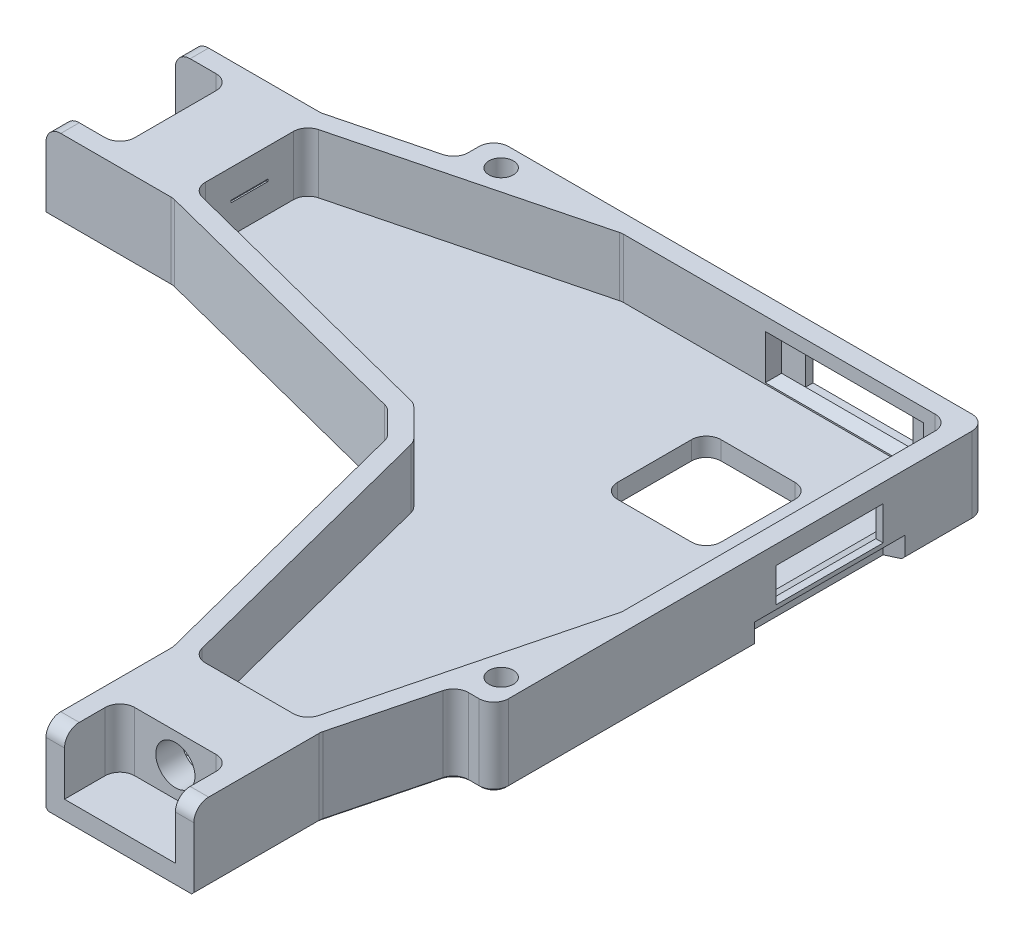
SolidWorks part; units mm, degrees
ref_plane "Front Plane" through (0, 0, 0) normal (0, 0, 1) x (1, 0, 0)
ref_plane "Top Plane" through (0, 0, 0) normal (0, 1, 0) x (1, 0, 0)
ref_plane "Right Plane" through (0, 0, 0) normal (1, 0, 0) x (0, 0, -1)
sketch "x Sensor" plane through (0, 0, 0) normal (0, 0, 1) x (1, 0, 0)
  line L0 (-13, 0) -> (0, 0) construction
  line L1 (-22.5, 1.5) -> (-13, 1.5)
  line L2 (-22.5, 1.5) -> (-22.5, -1.5)
  line L3 (-22.5, -1.5) -> (-13, -1.5)
  line L4 (-13, 1.5) -> (-13, -1.5)
  point P4 (-13, 0)
  dimension "D1" = 13
  dimension "D2" = 3
  dimension "D3" = 9.5
sketch "y Sensor" plane through (0, 0, 0) normal (1, 0, 0) x (0, 0, -1)
  line L0 (-13, 0) -> (0, 0) construction
  line L1 (-13, 1.5) -> (-22.5, 1.5)
  line L2 (-13, 1.5) -> (-13, -1.5)
  line L3 (-13, -1.5) -> (-22.5, -1.5)
  line L4 (-22.5, 1.5) -> (-22.5, -1.5)
  line L5 (0, 1.5) -> (0, -1.5) construction
  dimension "D1" = 9.5
  dimension "D2" = 13
ref_plane "y LED plane" through (-80, 0, 0) normal (1, 0, 0) x (0, 0, -1)
ref_plane "x LED plane" through (0, 0, 80) normal (0, 0, 1) x (1, 0, 0)
sketch "y LED" plane through (-80, 0, 0) normal (1, 0, 0) x (0, 0, -1)
  line L0 (-17.75, 1.5) -> (-17.75, -1.5) construction
  line L1 (-13, 1.5) -> (-22.5, 1.5) construction
  line L2 (-13, -1.5) -> (-22.5, -1.5) construction
  line L3 (-25.25, 0) -> (-10.25, 0) construction
  line L4 (-13, 0) -> (0, 0) construction
  point P10 (-17.75, 0)
  point P11 (-17.75, 0)
  dimension "D1" = 15
sketch "x LED" plane through (0, 0, 80) normal (0, 0, 1) x (1, 0, 0)
  line L0 (-17.75, 1.5) -> (-17.75, -1.5) construction
  line L1 (-22.5, 1.5) -> (-13, 1.5) construction
  line L2 (-22.5, -1.5) -> (-13, -1.5) construction
  line L3 (-25.25, 0) -> (-10.25, 0) construction
  point P9 (-17.75, 0)
  point P10 (-17.75, 0)
  dimension "D1" = 15
ref_plane "y LED cross-plane" through (0, 0, 17.75) normal (0, 0, 1) x (0, -1, 0)
ref_plane "x LED cross-plane" through (-17.75, 0, 0) normal (1, 0, 0) x (0, -1, 0)
ref_plane "Floor plane" through (0, -4, 0) normal (0, 1, 0) x (1, 0, 0)
ref_plane "Ceiling plane" through (0, 4, 0) normal (0, 1, 0) x (1, 0, 0)
sketch "Sketch10" plane through (0, -4, 0) normal (0, 1, 0) x (1, 0, 0)
  line L0 (0, 0) -> (-40, 0)
  line L1 (-40, 0) -> (-80, -10.25)
  line L2 (-80, -25.25) -> (-80, -10.25) construction
  line L3 (-80, -10.25) -> (-95, -10.25)
  line L4 (-95, -10.25) -> (-95, -25.25) construction
  line L5 (-95, -25.25) -> (-80, -25.25)
  line L6 (-80, -25.25) -> (-40, -35.5)
  line L7 (-40, -35.5) -> (-35.5, -40)
  line L8 (-35.5, -40) -> (-25.25, -80)
  line L9 (-25.25, -80) -> (-10.25, -80) construction
  line L10 (-25.25, -80) -> (-25.25, -95)
  line L11 (-25.25, -95) -> (-10.25, -95) construction
  line L12 (-10.25, -95) -> (-10.25, -80)
  line L13 (-10.25, -80) -> (0, -40)
  line L14 (0, -40) -> (0, 0)
  line L15 (-95, -17.75) -> (-65.0259, -17.75) construction
  line L16 (-17.75, -95) -> (-17.75, -69.9842) construction
  line L17 (-40.3152, 2.5) -> (-80.3152, -7.75)
  line L18 (-80.3152, -7.75) -> (-97.5, -7.75)
  line L19 (-97.5, -7.75) -> (-97.5, -10.25)
  line L20 (-97.5, -27.75) -> (-80.3152, -27.75)
  line L21 (-80.3152, -27.75) -> (-41.2837, -37.7518)
  line L22 (-41.2837, -37.7518) -> (-37.7518, -41.2837)
  line L23 (-37.7518, -41.2837) -> (-27.75, -80.3152)
  line L24 (-27.75, -80.3152) -> (-27.75, -97.5)
  line L25 (-27.75, -97.5) -> (-25.25, -97.5)
  line L26 (-7.75, -97.5) -> (-7.75, -80.3152)
  line L27 (-7.75, -80.3152) -> (2.5, -40.3152)
  line L28 (2.5, -40.3152) -> (2.5, 2.5)
  line L29 (2.5, 2.5) -> (-40.3152, 2.5)
  line L30 (-95, -10.25) -> (-97.5, -10.25)
  line L31 (-95, -25.25) -> (-97.5, -25.25)
  line L32 (-97.5, -10.25) -> (-97.5, -25.25) construction
  line L33 (-97.5, -7.75) -> (-97.5, -27.75) construction
  line L34 (-97.5, -25.25) -> (-97.5, -27.75)
  line L35 (-25.25, -95) -> (-25.25, -97.5)
  line L36 (-10.25, -95) -> (-10.25, -97.5)
  line L37 (-25.25, -97.5) -> (-10.25, -97.5) construction
  line L38 (-27.75, -97.5) -> (-7.75, -97.5) construction
  line L39 (-10.25, -97.5) -> (-7.75, -97.5)
  dimension "D1" = 45
  dimension "D2" = 40
  dimension "D3" = 15
  dimension "D4" = 2.5
sketch "Max Shadows" plane through (0, 0, 0) normal (0, 1, 0) x (1, 0, 0)
  line L0 (-80, -17.75) -> (0, -13) construction
  line L1 (0, -13) -> (0, -22.5) construction
  line L2 (0, -22.5) -> (-80, -17.75) construction
  line L3 (0, -40) -> (0, 0) construction
  line L4 (-17.75, -80) -> (-22.5, 0) construction
  line L5 (-25.25, -80) -> (-10.25, -80) construction
  line L6 (-22.5, 0) -> (-13, 0) construction
  line L7 (0, 0) -> (-40, 0) construction
  line L8 (-17.75, -80) -> (-13, 0) construction
extrude "Boss-Extrude3" add sketch "Sketch10" along normal up to surface (8 mm away) up to plane "Ceiling plane"
sketch "Sketch12" plane through (0, -4, 0) normal (0, 1, 0) x (1, 0, 0)
  line L0 (-97.5, -10.25) -> (-97.5, -25.25) construction
  line L1 (-97.5, -7.75) -> (-97.5, -10.25) construction
  line L2 (-80.3152, -7.75) -> (-97.5, -7.75) construction
  line L3 (-40.3152, 2.5) -> (-80.3152, -7.75) construction
  line L4 (2.5, 2.5) -> (-40.3152, 2.5) construction
  line L5 (2.5, -40.3152) -> (2.5, 2.5) construction
  line L6 (-7.75, -80.3152) -> (2.5, -40.3152) construction
  line L7 (-7.75, -97.5) -> (-7.75, -80.3152) construction
  line L8 (-10.25, -97.5) -> (-7.75, -97.5) construction
  line L9 (-25.25, -97.5) -> (-10.25, -97.5) construction
  line L10 (-27.75, -97.5) -> (-25.25, -97.5) construction
  line L11 (-27.75, -80.3152) -> (-27.75, -97.5) construction
  line L12 (-37.7518, -41.2837) -> (-27.75, -80.3152) construction
  line L13 (-97.5, -25.25) -> (-97.5, -27.75) construction
  line L14 (-97.5, -27.75) -> (-80.3152, -27.75) construction
  line L15 (-80.3152, -27.75) -> (-41.2837, -37.7518) construction
  line L16 (-41.2837, -37.7518) -> (-37.7518, -41.2837) construction
  line L17 (-97.5, -10.25) -> (-97.5, -25.25)
  line L18 (-97.5, -7.75) -> (-97.5, -10.25)
  line L19 (-80.3152, -7.75) -> (-97.5, -7.75)
  line L20 (-40.3152, 2.5) -> (-80.3152, -7.75)
  line L21 (2.5, 2.5) -> (-40.3152, 2.5)
  line L22 (2.5, -40.3152) -> (2.5, 2.5)
  line L23 (-7.75, -80.3152) -> (2.5, -40.3152)
  line L24 (-7.75, -97.5) -> (-7.75, -80.3152)
  line L25 (-10.25, -97.5) -> (-7.75, -97.5)
  line L26 (-25.25, -97.5) -> (-10.25, -97.5)
  line L27 (-27.75, -97.5) -> (-25.25, -97.5)
  line L28 (-27.75, -80.3152) -> (-27.75, -97.5)
  line L29 (-37.7518, -41.2837) -> (-27.75, -80.3152)
  line L30 (-97.5, -25.25) -> (-97.5, -27.75)
  line L31 (-97.5, -27.75) -> (-80.3152, -27.75)
  line L32 (-80.3152, -27.75) -> (-41.2837, -37.7518)
  line L33 (-41.2837, -37.7518) -> (-37.7518, -41.2837)
extrude "Boss-Extrude4" add sketch "Sketch12" against normal blind 2.5
sketch "Sketch13" plane through (0, 0, 17.75) normal (0, 0, 1) x (0, -1, 0)
  line L0 (-4, -80) -> (-0.15, -80)
  line L1 (4, -80) -> (4, -84.05)
  line L2 (4, -97.5) -> (4, -80) construction
  line L3 (-4, -80) -> (4, -80) construction
  line L5 (0.15, -80) -> (4, -80)
  line L6 (-0.15, -80) -> (0.15, -80) construction
  line L8 (-0.15, -80) -> (-0.15, -80.2)
  line L9 (-4, -80) -> (-4, -90)
  line L10 (-4, -97.5) -> (-4, -80) construction
  line L11 (-4, -90) -> (4, -90)
  line L12 (4, -90) -> (4, -86.5)
  line L13 (4, -86.5) -> (-3, -86.5)
  line L14 (-3, -86.5) -> (-3, -83.05)
  line L15 (-0.15, -80.2) -> (-3, -83.05)
  line L16 (0, -80) -> (0, -86.5) construction
  line L17 (-2.5, -90) -> (-2.5, -86.5) construction
  line L18 (-2.5, -86.5) -> (-2.5, -85.2) construction
  line L19 (2.5, -90) -> (2.5, -86.5) construction
  line L20 (2.5, -86.5) -> (2.5, -85.2) construction
  line L21 (0.15, -80) -> (0.15, -80.2)
  line L22 (0.15, -80.2) -> (4, -84.05)
  arc A0 (-2.5, -85.2) -> (2.5, -85.2) centre (0, -85.2) cw construction
  point P13 (0, -80)
  point P26 (0, -82.7)
  dimension "D3" = 7.3
  dimension "D1" = 0.3
  dimension "D2" = 1
  dimension "D4" = 5
  dimension "D5" = 45
  dimension "D6" = 6.5
  dimension "D7" = 10
  dimension "D8" = 0.2
extrude "Boss-Extrude5" add sketch "Sketch13" along normal up to next and the other way up to next
sketch "Sketch14" plane through (-90, 0, 0) normal (-1, 0, 0) x (0, 0, 1)
  line L0 (17.75, 1.5) -> (17.75, -1.5) construction
  circle A0 centre (17.75, 0) radius 2.65
  dimension "D1" = 5.3
extrude "Cut-Extrude1" cut sketch "Sketch14" against normal up to next
sketch "Sketch15" plane through (-17.75, 0, 0) normal (1, 0, 0) x (0, -1, 0)
  line L0 (-4, -80) -> (-0.15, -80)
  line L1 (4, -80) -> (4, -84.05)
  line L2 (4, -80) -> (4, -97.5) construction
  line L3 (-4, -80) -> (4, -80) construction
  line L5 (0.15, -80) -> (4, -80)
  line L6 (-0.15, -80) -> (0.15, -80) construction
  line L8 (-0.15, -80) -> (-0.15, -80.2)
  line L9 (-4, -80) -> (-4, -90)
  line L11 (-4, -90) -> (4, -90)
  line L12 (4, -90) -> (4, -86.5)
  line L13 (4, -86.5) -> (-3, -86.5)
  line L14 (-3, -86.5) -> (-3, -83.05)
  line L15 (-0.15, -80.2) -> (-3, -83.05)
  line L16 (0, -80) -> (0, -86.5) construction
  line L17 (-2.5, -90) -> (-2.5, -86.5) construction
  line L18 (-2.5, -86.5) -> (-2.5, -85.2) construction
  line L19 (2.5, -90) -> (2.5, -86.5) construction
  line L20 (2.5, -86.5) -> (2.5, -85.2) construction
  line L21 (0.15, -80) -> (0.15, -80.2)
  line L22 (0.15, -80.2) -> (4, -84.05)
  arc A0 (-2.5, -85.2) -> (2.5, -85.2) centre (0, -85.2) cw construction
extrude "Boss-Extrude6" add sketch "Sketch15" along normal up to next and the other way up to next
sketch "Sketch16" plane through (0, 0, 90) normal (0, 0, -1) x (-1, 0, 0)
  circle A0 centre (17.75, 0) radius 2.65
extrude "Cut-Extrude2" cut sketch "Sketch16" along normal up to next
sketch "Sketch18" plane through (0, 0, -2.5) normal (0, 0, -1) x (-1, 0, 0)
  line L0 (-2.5, -6.5) -> (40.3152, -6.5) construction
  line L1 (-2.5, 4) -> (80.3152, 4)
  line L2 (-2.5, 4) -> (-2.5, -6.5)
  line L3 (-2.5, -6.5) -> (80.3152, -6.5)
  line L4 (80.3152, 4) -> (80.3152, -6.5)
  line L6 (80.3152, 4) -> (80.3152, -6.5) construction
extrude "Cut-Extrude4" cut sketch "Sketch18" against normal offset from surface (1.5 mm away) 1 up to face at (-20, 0, 0)
sketch "Sketch20" plane through (2.5, 0, 0) normal (1, 0, 0) x (0, 0, -1)
  line L0 (-40.3152, 4) -> (1, 4) construction
  line L1 (1, -6.5) -> (-80.3152, -6.5)
  line L2 (1, -6.5) -> (1, 4)
  line L3 (1, 4) -> (-80.3152, 4)
  line L4 (-80.3152, -6.5) -> (-80.3152, 4)
  line L5 (-80.3152, 4) -> (-80.3152, -6.5) construction
extrude "Cut-Extrude6" cut sketch "Sketch20" against normal offset from surface (1.5 mm away) 1 contours L1 L4 L3 L2 up to face at (0, 0, 20)
sketch "Sketch21" plane through (0, 0, 0) normal (0, 0, 1) x (1, 0, 0)
  line L0 (-40, -4) -> (-50.0713, -4)
  line L1 (-50.0713, -4) -> (-50.0713, 4)
  line L2 (-50.0713, 4) -> (-40, 4)
  line L3 (-46.1689, 4) -> (-80.3152, 4) construction
  line L4 (0, 4) -> (-40, 4)
  line L5 (-40, 4) -> (-40, -4)
  line L6 (-40, -4) -> (0, -4)
  line L7 (0, -4) -> (0, 4)
  line L8 (0, 4) -> (-40, 4)
  line L10 (-40, -4) -> (0, -4)
  line L11 (0, -4) -> (0, 4)
  dimension "D1" = 0
extrude "Boss-Extrude7" add sketch "Sketch21" along normal offset from surface (1.5 mm away) 2.5 up to face at (-22.5844, -1.25, -1)
sketch "Sketch22" plane through (0, 0, 0) normal (-1, 0, 0) x (0, 0, 1)
  line L0 (40, -4) -> (50.0713, -4)
  line L1 (50.0713, -4) -> (50.0713, 4)
  line L2 (50.0713, 4) -> (40, 4)
  line L4 (1.5, 4) -> (1.5, -4)
  line L5 (1.5, -4) -> (40, -4)
  line L6 (40, -4) -> (40, 4)
  line L7 (40, 4) -> (1.5, 4)
  line L8 (1.5, 4) -> (1.5, -4)
  line L9 (1.5, -4) -> (40, -4)
  line L11 (40, 4) -> (1.5, 4)
  dimension "D1" = 0
extrude "Boss-Extrude8" add sketch "Sketch22" along normal offset from surface (1.5 mm away) 2.5 up to face at (1, -1.25, 22.5844)
sketch "Sketch17" plane through (0, 0, 0) normal (0, 0, 1) x (1, 0, 0)
  line L1 (-8, -3.1) -> (-22.5, -3.1)
  line L2 (-8, -3.1) -> (-8, 1.5)
  line L3 (-8, 1.5) -> (-22.5, 1.5)
  line L4 (-22.5, -3.1) -> (-22.5, 1.5)
  dimension "D1" = 14.5
  dimension "D2" = 4.6
extrude "Cut-Extrude3" cut sketch "Sketch17" against normal through all and the other way up to next
sketch "Sketch19" plane through (0, 0, 0) normal (1, 0, 0) x (0, 0, -1)
  line L1 (-13, -3.1) -> (-27.5, -3.1)
  line L2 (-13, -3.1) -> (-13, 1.5)
  line L3 (-13, 1.5) -> (-27.5, 1.5)
  line L4 (-27.5, -3.1) -> (-27.5, 1.5)
  dimension "D1" = 14.5
  dimension "D2" = 4.6
extrude "Cut-Extrude5" cut sketch "Sketch19" along normal through all and the other way up to next
sketch "Sketch23" plane through (-1.5, 0, 0) normal (-1, 0, 0) x (0, 0, 1)
  line L0 (27.5, -3.1) -> (13, -3.1) construction
  line L1 (10.25, 1.5) -> (30.25, 1.5)
  line L2 (10.25, 1.5) -> (10.25, -3.1)
  line L3 (10.25, -3.1) -> (30.25, -3.1)
  line L4 (30.25, 1.5) -> (30.25, -3.1)
  point P4 (20.25, -3.1)
  point P7 (20.25, -3.1)
  dimension "D1" = 20
extrude "Cut-Extrude7" cut sketch "Sketch23" against normal up to surface (1.5 mm away) up to plane "Right Plane"
sketch "Sketch25" plane through (-36, 0, 1.5) normal (0, 0, 1) x (1, 0, 0)
  line L0 (13.5, 1.5) -> (28, 1.5) construction
  line L1 (10.25, 1.5) -> (30.25, 1.5)
  line L2 (10.25, 1.5) -> (10.25, -3.1)
  line L3 (10.25, -3.1) -> (30.25, -3.1)
  line L4 (30.25, 1.5) -> (30.25, -3.1)
extrude "Cut-Extrude9" cut sketch "Sketch25" against normal up to surface (1.5 mm away) up to plane "Front Plane"
chamfer "Chamfer2" distance 1.5 angle 25 8 edges at (-1.5, -3.1, 20.25) (-1.5, -0.8, 30.25) (-1.5, 1.5, 20.25) (-1.5, -0.8, 10.25) (-5.75, -0.8, 1.5) (-15.75, 1.5, 1.5) (-25.75, -0.8, 1.5) (-15.75, -3.1, 1.5) first distance on face at (-0.125, -3.1, 20.25) first distance on face at (-0.75, -0.8, 30.25) first distance on face at (-0.125, 1.5, 20.25) first distance on face at (-0.75, -0.8, 10.25) first distance on face at (-5.75, -0.8, 0.75) first distance on face at (-15.5, 1.5, 0.125) first distance on face at (-25.75, -0.8, 0.75) first distance on face at (-15.5, -3.1, 0.125)
sketch "Sketch28" plane through (0, 0, -1) normal (0, 0, -1) x (-1, 0, 0)
  line L0 (-1, -6.5) -> (46.1689, -6.5) construction
  line L1 (24.5, -4.6) -> (6, -4.6)
  line L2 (24.5, -4.6) -> (24.5, -6.5)
  line L3 (24.5, -6.5) -> (6, -6.5)
  line L4 (6, -4.6) -> (6, -6.5)
  line L7 (22.5, -3.1) -> (8, -3.1) construction
  line L8 (8, -3.1) -> (8, 1.5) construction
  line L10 (22.5, 1.5) -> (22.5, -3.1) construction
  dimension "D1" = 1.5
  dimension "D2" = 2
  dimension "D3" = 2
extrude "Cut-Extrude10" cut sketch "Sketch28" against normal blind 2
sketch "Sketch29" plane through (1, 0, 5) normal (-1, 0, 0) x (0, 0, 1)
  line L0 (22.5, -3.1) -> (8, -3.1) construction
  line L1 (24.5, -4.6) -> (6, -4.6)
  line L2 (24.5, -4.6) -> (24.5, -6.5)
  line L3 (24.5, -6.5) -> (6, -6.5)
  line L4 (6, -4.6) -> (6, -6.5)
  line L5 (22.5, 1.5) -> (22.5, -3.1) construction
  line L6 (8, -3.1) -> (8, 1.5) construction
  line L7 (41.1689, -6.5) -> (-6, -6.5) construction
  dimension "D1" = 1.5
  dimension "D2" = 2
  dimension "D3" = 2
extrude "Cut-Extrude11" cut sketch "Sketch29" along normal blind 2
chamfer "Chamfer3" distance 2 angle 25 6 edges at (-24.5, -5.55, -1) (-15.25, -4.6, -1) (-6, -5.55, -1) (1, -5.55, 11) (1, -5.55, 29.5) (1, -4.6, 20.25) first distance on face at (-24.5, -5.55, 0) first distance on face at (-15.25, -4.6, 0) first distance on face at (-6, -5.55, 0) first distance on face at (0, -5.55, 11) first distance on face at (0, -5.55, 29.5) first distance on face at (0, -4.6, 20.25)
sketch "Sketch30" plane through (0, -4, 0) normal (0, 1, 0) x (1, 0, 0)
  line L0 (-13.8206, -13.8206) -> (-21.2389, -21.2389) construction
  line L1 (-14.2856, -21.6518) -> (-21.6518, -14.2856) construction
  line L2 (-80, -17.75) -> (0, -13) construction
  line L3 (-17.75, -80) -> (-22.5, 0) construction
  line L4 (0, -22.5) -> (-80, -17.75) construction
  line L5 (-17.75, -80) -> (-13, 0) construction
  line L7 (-10.9687, -10.9687) -> (-24.9687, -10.9687)
  line L8 (-10.9687, -10.9687) -> (-10.9687, -24.9687)
  line L9 (-10.9687, -24.9687) -> (-24.9687, -24.9687)
  line L10 (-24.9687, -10.9687) -> (-24.9687, -24.9687)
  line L11 (-10.9687, -10.9687) -> (-24.9687, -24.9687) construction
  line L12 (-10.9687, -24.9687) -> (-24.9687, -10.9687) construction
  point P12 (-17.9687, -17.9687)
  point P13 (-17.9687, -17.9687)
  dimension "D1" = 14
extrude "Cut-Extrude12" cut sketch "Sketch30" against normal through all
fillet "Fillet1" radius 2 4 edges at (-10.9687, -5.25, 10.9687) (-10.9687, -5.25, 24.9687) (-24.9687, -5.25, 24.9687) (-24.9687, -5.25, 10.9687)
sketch "Sketch31" plane through (0, -0.15, 0) normal (0, 1, 0) x (1, 0, 0)
  line L0 (-80.2, -10.25) -> (-80.2, -25.25) construction
  line L1 (-80, -10.25) -> (-80.2, -10.25)
  line L2 (-80, -10.25) -> (-80, -15.25)
  line L3 (-80, -15.25) -> (-80.2, -15.25)
  line L4 (-80.2, -10.25) -> (-80.2, -15.25)
  line L6 (-80, -25.25) -> (-80.2, -25.25)
  line L7 (-80, -25.25) -> (-80, -20.25)
  line L8 (-80, -20.25) -> (-80.2, -20.25)
  line L9 (-80.2, -25.25) -> (-80.2, -20.25)
  dimension "D1" = 5
extrude "Boss-Extrude9" add sketch "Sketch31" along normal up to next
sketch "Sketch32" plane through (0, -0.15, 0) normal (0, 1, 0) x (1, 0, 0)
  line L0 (-25.25, -80.2) -> (-10.25, -80.2) construction
  line L1 (-25.25, -80) -> (-20.25, -80)
  line L2 (-25.25, -80) -> (-25.25, -80.2)
  line L3 (-25.25, -80.2) -> (-20.25, -80.2)
  line L4 (-20.25, -80) -> (-20.25, -80.2)
  line L6 (-10.25, -80) -> (-15.25, -80)
  line L7 (-10.25, -80) -> (-10.25, -80.2)
  line L8 (-10.25, -80.2) -> (-15.25, -80.2)
  line L9 (-15.25, -80) -> (-15.25, -80.2)
  dimension "D1" = 5
extrude "Boss-Extrude10" add sketch "Sketch32" along normal up to next
sketch "Sketch33" plane through (0, -6.5, 0) normal (0, -1, 0) x (1, 0, 0)
  line L0 (1, -1) -> (-39.5178, 39.5178) construction
  line L1 (-41.2837, 37.7518) -> (-37.7518, 41.2837) construction
  line L2 (-46.1689, -1) -> (-80.3152, 7.75) construction
  line L3 (-46.1689, -1) -> (-65.6811, -1)
  line L4 (-46.1689, -1) -> (-65.6811, 4)
  line L5 (1, 65.6811) -> (-4, 65.6811)
  line L6 (-65.6811, -1) -> (-65.6811, 4)
  line L7 (1, 46.1689) -> (-4, 65.6811)
  line L8 (1, 46.1689) -> (1, 65.6811)
  dimension "D1" = 5
extrude "Boss-Extrude11" add sketch "Sketch33" against normal up to surface (10.5 mm away) up to face at (-47.4207, 4, 47.4207)
sketch "Sketch35" plane through (0, 4, 0) normal (0, 1, 0) x (1, 0, 0)
  line L0 (1, 1) -> (-39.5178, -39.5178) construction
  line L1 (-41.2837, -37.7518) -> (-37.7518, -41.2837) construction
  line L2 (-65.6811, -4) -> (-65.6811, 1) construction
  line L3 (1, 1) -> (-65.6811, 1) construction
  circle A0 centre (-61.6811, -2) radius 1.65
  circle A1 centre (-2, -61.6811) radius 1.65
  dimension "D1" = 4
  dimension "D3" = 3.3
  dimension "D2" = 3
extrude "Cut-Extrude13" cut sketch "Sketch35" against normal through all
fillet "Fillet2" radius 2 28 edges at (-90, 0, 10.25) (-90, 0, 25.25) (-25.25, 0, 90) (-10.25, 0, 90) (-97.5, 4, 9) (-97.5, 4, 26.5) (-80.3152, -1.25, 7.75) (1, -1.25, -1) (-7.75, -1.25, 80.3152) (-27.75, -1.25, 80.3152) (-37.7518, -1.25, 41.2837) (-41.2837, -1.25, 37.7518) (-80.3152, -1.25, 27.75) (-40, 0, 35.5) (-1.5, 0, 45.8537) (-35.5, 0, 40) (-1.5, 0, 1.5) (-45.8537, 0, 1.5) (-80, 0, 10.25) (-80, 0, 25.25) (-10.25, 0, 80) (-25.25, 0, 80) (-65.6811, -1.25, -1) (-65.6811, -1.25, 4) (1, -1.25, 65.6811) (-4, -1.25, 65.6811) (-9, 4, 97.5) (-26.5, 4, 97.5)
chamfer "Chamfer4" distance 0.3 angle 45 26 edges at (-44.5568, -6.5, -1) (-65.0953, -6.5, -0.4142) (-65.6811, -6.5, 1.7239) (-66.1011, -6.5, 3.6741) (-73.6278, -6.5, 6.0363) (-80.3172, -6.5, 7.7343) (-89.0337, -6.5, 7.75) (-3.0337, -6.5, -1) (0.4142, -6.5, -0.4142) (1, -6.5, 5.5337) (1, -6.5, 47.0568) (0.4142, -6.5, 65.0953) (-1.7239, -6.5, 65.6811) (-3.6741, -6.5, 66.1011) (-6.0363, -6.5, 73.6278) (-7.7343, -6.5, 80.3172) (-7.75, -6.5, 89.0337) (-27.75, -6.5, 89.0337) (-27.7657, -6.5, 80.3172) (-32.7142, -6.5, 60.9426) (-37.8158, -6.5, 41.3202) (-39.5178, -6.5, 39.5178) (-41.3202, -6.5, 37.8158) (-60.9426, -6.5, 32.7142) (-80.3172, -6.5, 27.7657) (-89.0337, -6.5, 27.75)
